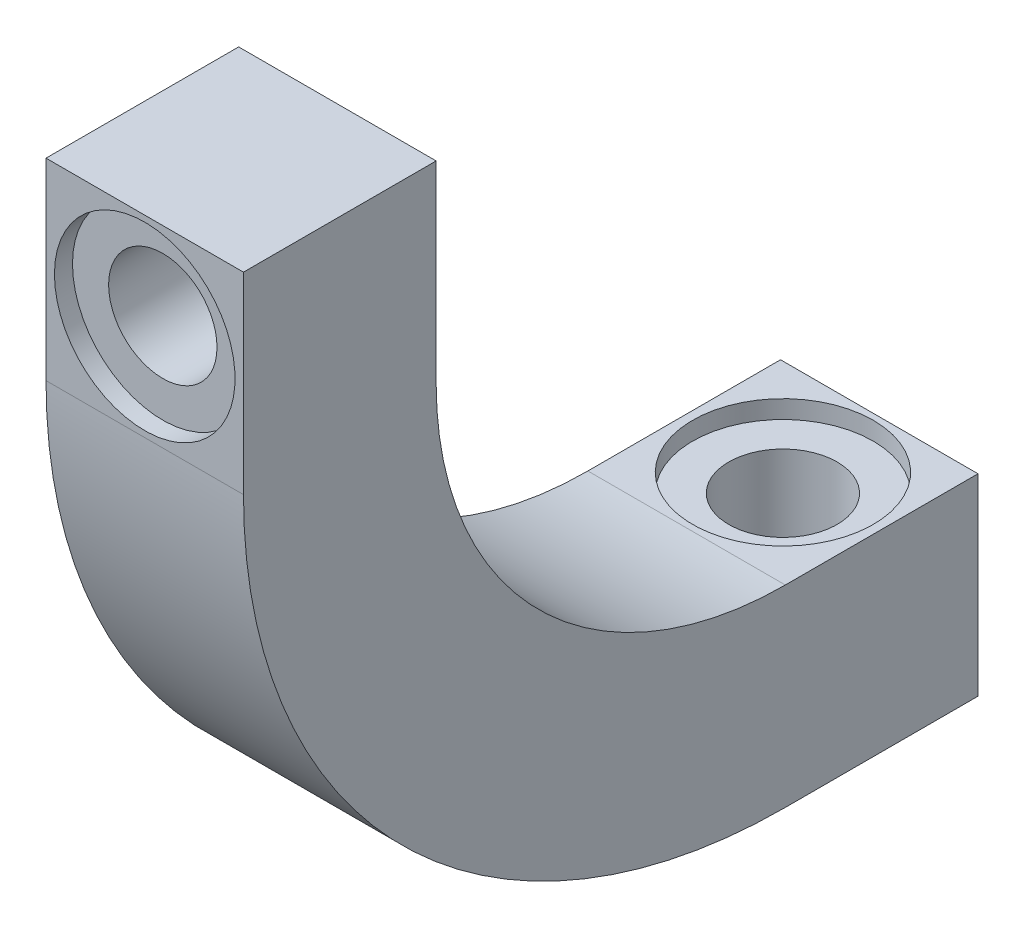
SolidWorks part; units mm, degrees
ref_plane "Front Plane" through (0, 0, 0) normal (0, 0, 1) x (1, 0, 0)
ref_plane "Top Plane" through (0, 0, 0) normal (0, 1, 0) x (1, 0, 0)
ref_plane "Right Plane" through (0, 0, 0) normal (1, 0, 0) x (0, 0, -1)
ref_axis "Z" through (0, 0, 22.75) along (0, 0, -1)
sketch "Sketch4" plane through (0, 0, 0) normal (0, 0, 1) x (1, 0, 0)
  circle A0 centre (0, 0) radius 17.5 construction
  dimension "D1" = 35
sketch "Sketch5" plane through (0, 0, 0) normal (1, 0, 0) x (0, 0, -1)
  line L0 (-18.5, 4) -> (-18.5, 0)
  line L1 (-18.5, 0) -> (-18.5, -4)
  line L2 (-26.5, -4) -> (-26.5, 4)
  line L6 (-26.5, 4) -> (-18.5, 4)
  line L12 (-22.75, 0) -> (-13.0351, 0) construction
  line L13 (0, 0) -> (-14.9091, -14.9091) construction
  line L14 (0, 0) -> (7.0065, 0) construction
  line L15 (0, -18.5) -> (-4, -18.5)
  line L16 (4, -18.5) -> (0, -18.5)
  line L17 (-4, -26.5) -> (4, -26.5)
  line L18 (4, -26.5) -> (4, -18.5)
  circle A0 centre (0, 0) radius 14 construction
  arc A1 (-18.5, -4) -> (-4, -18.5) centre (-4, -4) ccw
  arc A2 (-26.5, -4) -> (-4, -26.5) centre (-4, -4) ccw
  point P2 (9.4307, -21)
  point P4 (0, -2.1363)
  dimension "D1" = 28
  dimension "D4" = 4
  dimension "D2" = 45
  dimension "D3" = 8
  dimension "D5" = 18.5
sketch "Sketch6" plane through (0, 0, 0) normal (0, 1, 0) x (1, 0, 0)
  circle A0 centre (0, 0) radius 17.5 construction
  dimension "D1" = 35
extrude "Boss-Extrude1" add sketch "Sketch5" along normal blind 4.1 and the other way blind 4.1
sketch "Sketch7" plane through (0, 0, 0) normal (0, 0, 1) x (1, 0, 0)
  circle A0 centre (0, 0) radius 1.75
  dimension "D1" = 3.5
extrude "Cut-Extrude1" cut sketch "Sketch7" along normal through all
sketch "Sketch8" plane through (0, 0, 0) normal (0, 1, 0) x (1, 0, 0)
  circle A0 centre (0, 0) radius 1.75
  dimension "D1" = 3.5
extrude "Cut-Extrude2" cut sketch "Sketch8" against normal through all
ref_axis "Y" through (0, -9.3489, 0) along (0, -1, 0)
sketch "Sketch9" plane through (0, -18.5, 0) normal (0, 1, 0) x (1, 0, 0)
  circle A0 centre (0, 0) radius 3
  dimension "D1" = 6
extrude "Cut-Extrude4" [suppressed] cut sketch "Sketch9" against normal blind 2.5
sketch "Sketch10" plane through (0, 0, 18.5) normal (0, 0, -1) x (-1, 0, 0)
  circle A0 centre (0, 0) radius 3
  dimension "D1" = 6
extrude "Cut-Extrude5" [suppressed] cut sketch "Sketch10" against normal blind 2.5
sketch "Sketch11" plane through (0, -18.5, 0) normal (0, -1, 0) x (1, 0, 0)
  circle A0 centre (0, 0) radius 2.25
  point P2 (-13.2782, 2.4361)
  dimension "D1" = 4.5
extrude "Cut-Extrude6" cut sketch "Sketch11" along normal blind 6
sketch "Sketch12" plane through (0, 0, 26.5) normal (0, 0, 1) x (1, 0, 0)
  circle A0 centre (0, 0) radius 2.25
  point P2 (-9.7185, 1.8171)
  point P4 (0, 0)
  dimension "D1" = 4.5
extrude "Cut-Extrude7" cut sketch "Sketch12" against normal blind 6
sketch "Sketch13" plane through (0, -18.5, 0) normal (0, -1, 0) x (1, 0, 0)
  circle A0 centre (0, 0) radius 3.75
  point P2 (-7.7371, 1.4245)
  dimension "D1" = 7.5
extrude "Cut-Extrude8" cut sketch "Sketch13" along normal blind 0.75
ref_plane "Plane1" through (0, -18.5, 0) normal (0, 1, 0) x (1, 0, 0)
ref_axis "CX" through (0, -18.5, 4.4) along (0, 0, -1)
ref_plane "Plane2" through (0, 0, 0) normal (0, 0, -1) x (0, 1, 0)
ref_plane "Plane3" through (0, 0, 0) normal (1, 0, 0) x (0, 0, -1)
ref_axis "CZ" through (0, -8.7018, 0) along (0, -1, 0)
ref_axis "CY" through (-0.6471, -18.5, 0) along (1, 0, 0)
ref_point "CO"
sketch "Sketch14" plane through (0, 0, 26.5) normal (0, 0, -1) x (1, 0, 0)
  circle A0 centre (0, 0) radius 3.75
  point P2 (-7.7371, 1.4245)
  point P4 (-8.3097, 0.2916)
  dimension "D1" = 7.5
extrude "Cut-Extrude10" cut sketch "Sketch14" along normal blind 0.75
equation "\"rbracket-width\"= \"L2Thickness\" + 0.2"
equation "\"EyeCaptureRadius\"= ( \"EyeDiameter\" + \"EyeClearance\" ) / 2"
equation "\"rbracket_planetocenterline_dist\"= \"BasePlaneDistance\""
equation "\"EyeDiameter\" = 35"
equation "\"BasePlaneDistance\" = \"EyeDiameter\"/2+19.84"
equation "\"EyeClearance\" = 2"
equation "\"D1@Sketch4\"=\"EyeDiameter\""
equation "\"D1@Sketch6\"=\"EyeDiameter\""
equation "\"D1@Boss-Extrude1\"=\"rbracket-width\"/2"
equation "\"D2@Boss-Extrude1\"=\"rbracket-width\"/2"
equation "\"L2Thickness\" = 8"
equation "\"D3@Sketch5\"=\"L2Thickness\""
equation "\"D5@Sketch5\"=(\"EyeDiameter\"+\"EyeClearance\")/2"
equation "\"BearingThickness\"= 6"
equation "\"BearingOD\"= 4.5"
equation "\"OuterBearingProudDistance\"= 0"
equation "\"D1@Cut-Extrude7\"=\"BearingThickness\"-\"OuterBearingProudDistance\""
equation "\"D1@Cut-Extrude6\"=\"BearingThickness\" - \"OuterBearingProudDistance\""
equation "\"D1@Sketch11\"=\"BearingOD\""
equation "\"D1@Sketch12\"=\"BearingOD\""
